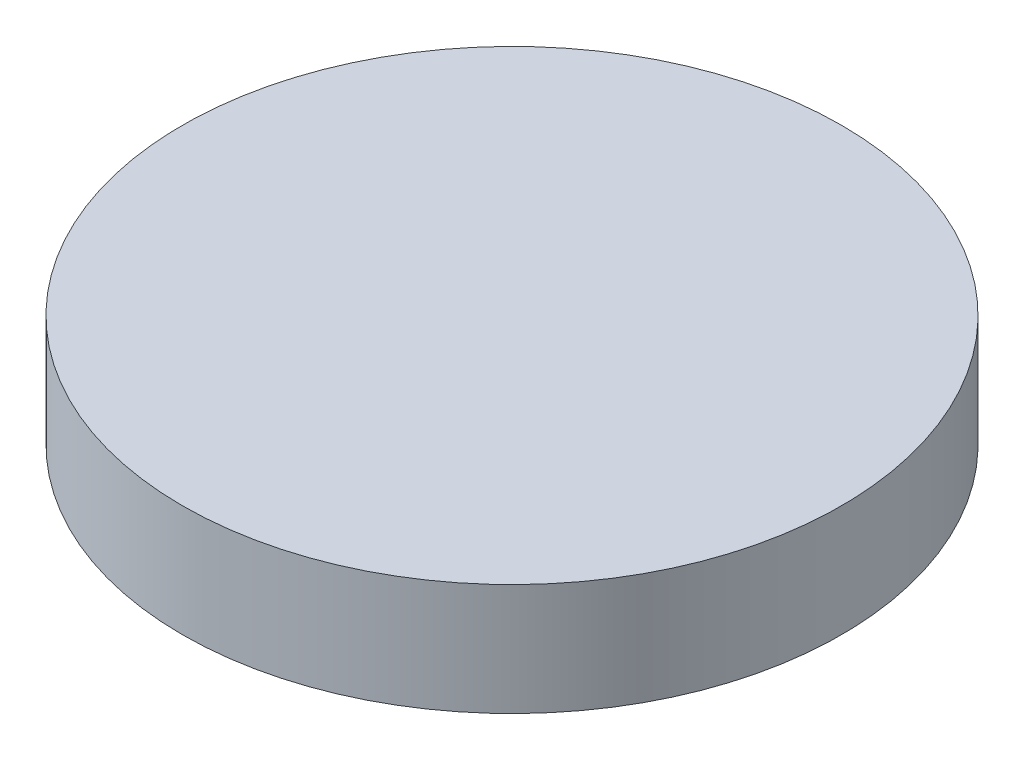
SolidWorks part; units mm, degrees
ref_plane "Front Plane" through (0, 0, 0) normal (0, 0, 1) x (1, 0, 0)
ref_plane "Top Plane" through (0, 0, 0) normal (0, 1, 0) x (1, 0, 0)
ref_plane "Right Plane" through (0, 0, 0) normal (1, 0, 0) x (0, 0, -1)
sketch "Sketch1" plane through (0, 0, 0) normal (0, 1, 0) x (1, 0, 0)
  circle A0 centre (0, 0) radius 37.465
  dimension "D1" = 74.93
extrude "Boss-Extrude1" add sketch "Sketch1" along normal blind 12.7
hole_wizard "M3 Clearance Hole1" positions "Sketch2" profile "Sketch3" hole size "M3" standard "DIN"
sketch "Sketch2" plane through (0, 0, 0) normal (0, -1, 0) x (-1, 0, 0)
  point P0 (0, 0)
sketch "Sketch3" plane through (0, 0, 0) normal (1, 0, 0) x (0, 0, -1)
  line L0 (0, 0) -> (0, 10.6735)
  line L1 (0, 10.6735) -> (1.7, 9.652)
  line L2 (1.7, 9.652) -> (1.7, 0.025)
  line L3 (1.7, 0.025) -> (1.725, 0)
  line L5 (1.725, 0) -> (0, 0)
  line L6 (-1.7, 0.025) -> (-1.725, 0) construction
  line L10 (0, 10.6735) -> (-1.7, 9.652) construction
  line L11 (0, -6.35) -> (0, 107.95) construction
  dimension "Hole Dia." = 3.4
  dimension "Hole Depth" = 9.652
  dimension "Near C'Sink Dia." = 3.45
  dimension "Near C'Sink Angle" = 90
  dimension "Drill Angle" = 118
thread "Thread1" pitch 0.5 method extrude profile "Thread Profile1" start angle 0, offset 0, length 10, pitch 0.5, diameter 3.4
ref_plane "Plane1" through (1.7, 0.025, 0) normal (0, 0, 1) x (1, 0, 0)
sketch "Thread Profile1" plane through (1.7, 0.025, 0) normal (0, 0, 1) x (1, 0, 0)
  line L0 (0, 0) -> (0, 0.5) construction
  line L11 (0, 0) -> (0, 0.4375)
  line L12 (0, 0.4375) -> (-0.2706, 0.2812)
  line L13 (-0.2706, 0.2812) -> (-0.2706, 0.1562)
  line L15 (-0.2706, 0.1562) -> (0, 0)
  line L17 (-0.2706, 0.2187) -> (0, 0.2187) construction
  point P2 (0, 0)
  dimension "Pitch" = 0.5
  dimension "Profile_Angle" = 60
  dimension "Profile_Land" = 0.125
  dimension "Profile_Height" = 0.2706
